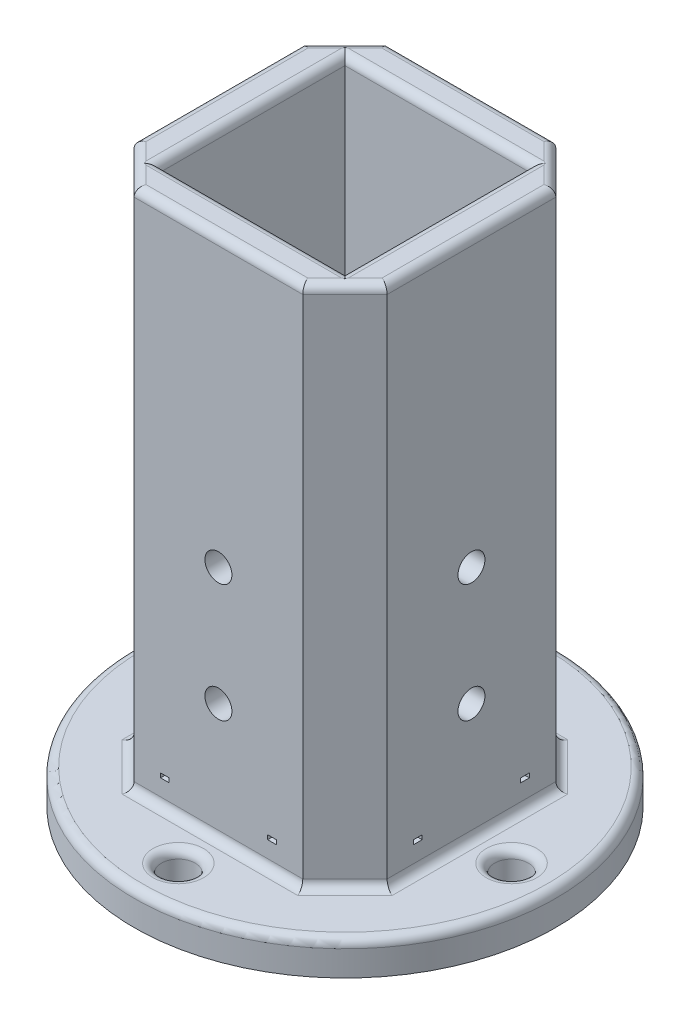
SolidWorks part; units mm, degrees
ref_plane "Front Plane" through (0, 0, 0) normal (0, 0, 1) x (1, 0, 0)
ref_plane "Top Plane" through (0, 0, 0) normal (0, 1, 0) x (1, 0, 0)
ref_plane "Right Plane" through (0, 0, 0) normal (1, 0, 0) x (0, 0, -1)
sketch "Sketch1" plane through (0, 0, 0) normal (0, 1, 0) x (1, 0, 0)
  line L1 (0, 0) -> (30, 0)
  line L2 (0, 0) -> (0, 30)
  line L3 (0, 30) -> (30, 30)
  line L4 (30, 0) -> (30, 30)
  dimension "D1" = 30
  dimension "D2" = 30
extrude "Boss-Extrude1" add sketch "Sketch1" along normal blind 62
shell "Shell1" thickness 4 removed face at (15, 0, -15) removed face at (15, 62, -15)
sketch "Sketch2" plane through (30, 0, 0) normal (1, 0, 0) x (0, 0, -1)
  line L0 (0, 0) -> (30, 0) construction
  circle A0 centre (15, 14) radius 1.6
  circle A2 centre (15, 28) radius 1.6
  point P4 (0, 0)
  point P8 (15, 0)
  dimension "D1" = 3.2
  dimension "D2" = 3.2
  dimension "D3" = 14
  dimension "D4" = 14
extrude "Cut-Extrude1" cut sketch "Sketch2" against normal blind 62
sketch "Sketch3" plane through (0, 0, 0) normal (0, -1, 0) x (1, 0, 0)
  line L0 (26, -26) -> (4, -26) construction
  line L9 (30, 0) -> (30, -30) construction
  line L11 (26, -4) -> (26, -26) construction
  line L12 (4, -26) -> (4, -4) construction
  line L13 (4, -4) -> (26, -4) construction
  line L14 (26, -26) -> (4, -26)
  line L15 (26, -4) -> (26, -26)
  line L16 (4, -26) -> (4, -4)
  line L17 (4, -4) -> (26, -4)
  circle A0 centre (15, -15) radius 25
  circle A1 centre (34.75, -15) radius 2
  circle A8 centre (15, -34.75) radius 2
  circle A9 centre (-4.75, -15) radius 2
  circle A10 centre (15, 4.75) radius 2
  point P7 (26, -15)
  point P15 (15, -26)
  point P23 (16.25, -11.25)
  point P24 (15, -15)
  dimension "D1" = 50
  dimension "D2" = 4
  dimension "D3" = 4.75
  dimension "D4" = 4
extrude "Boss-Extrude2" add sketch "Sketch3" along normal blind 4
pattern_circular "CirPattern1" count 2 over 90 about axis through (15, -4, -15) along (0, 1, 0) of "Cut-Extrude1"
chamfer "Chamfer1" distance 5 angle 45 4 edges at (0, 31, 0) (30, 31, 0) (30, 31, -30) (0, 31, -30)
fillet "Fillet1" radius 1 12 edges at (15, 62, -4) (26, 62, -15) (15, 62, -26) (4, 62, -15) (2.5, 62, -27.5) (15, 62, -30) (27.5, 62, -27.5) (30, 62, -15) (27.5, 62, -2.5) (15, 62, 0) (2.5, 62, -2.5) (0, 62, -15)
fillet "Fillet2" radius 1 13 edges at (34.75, 0, -17) (15, 0, -40) (2.5, 0, -2.5) (15, 0, 0) (27.5, 0, -2.5) (30, 0, -15) (27.5, 0, -27.5) (15, 0, -30) (2.5, 0, -27.5) (0, 0, -15) (15, 0, 2.75) (-4.75, 0, -17) (15, 0, -36.75)
sketch "Sketch4" plane through (4, 0, 0) normal (1, 0, 0) x (0, 0, -1)
  line L0 (8.14, 3.46) -> (9.16, 3.46)
  line L1 (9.16, 3.46) -> (9.16, 2.95)
  line L2 (9.16, 2.95) -> (8.14, 2.95)
  line L3 (8.14, 2.95) -> (8.14, 3.46)
  line L12 (21.86, 2.95) -> (21.86, 3.46)
  line L13 (21.86, 3.46) -> (20.84, 3.46)
  line L14 (20.84, 3.46) -> (20.84, 2.95)
  line L15 (20.84, 2.95) -> (21.86, 2.95)
extrude "Cut-Extrude2" cut sketch "Sketch4" against normal through all both and the other way through all
pattern_circular "CirPattern2" count 2 over 90 about axis through (15, -4, -15) along (0, -1, 0) of "Cut-Extrude2"
